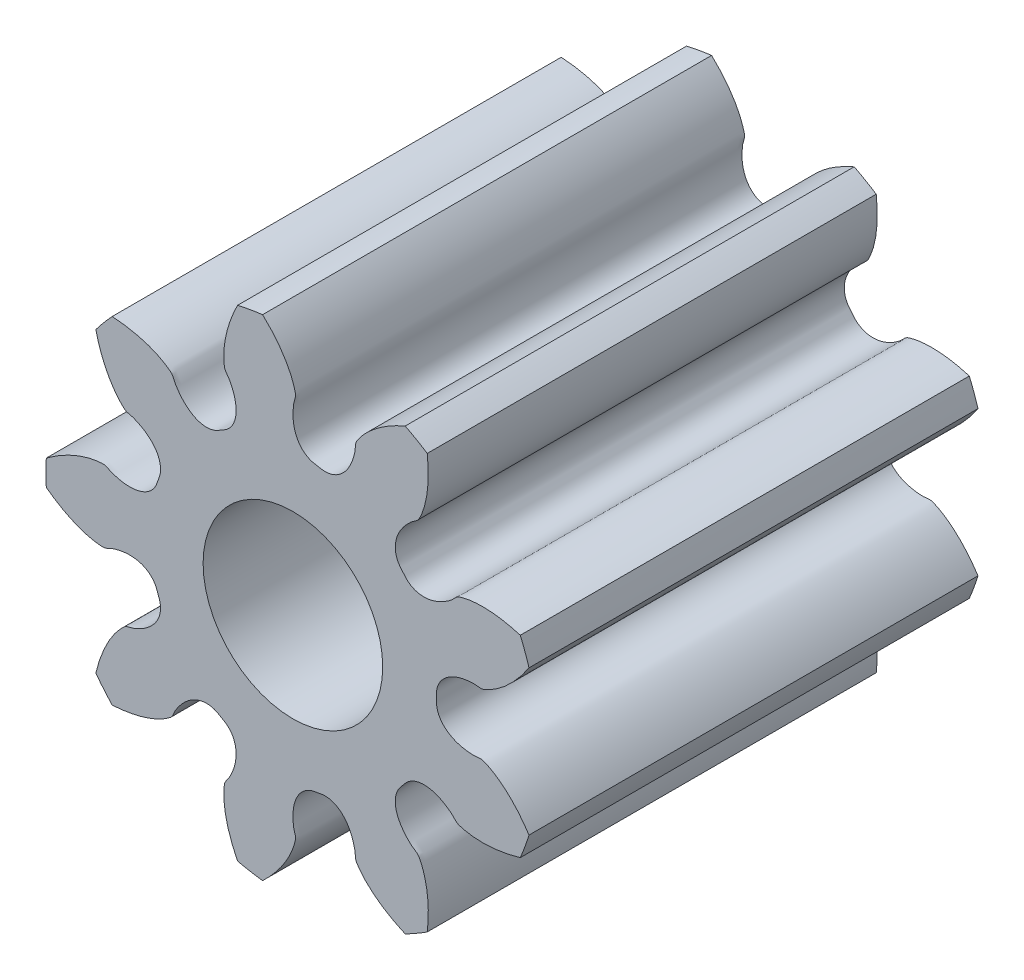
SolidWorks part; units mm, degrees
ref_plane "Front Plane" through (0, 0, 0) normal (0, 0, 1) x (1, 0, 0)
ref_plane "Top Plane" through (0, 0, 0) normal (0, 1, 0) x (1, 0, 0)
ref_plane "Right Plane" through (0, 0, 0) normal (1, 0, 0) x (0, 0, -1)
ref_axis "Axis1" through (0, 0, 55) along (0, 0, -1)
sketch "旋转草图小直齿轮" plane through (0, 0, 0) normal (1, 0, 0) x (0, 0, -1)
  line L0 (0, 0) -> (1, 0) construction
  line L1 (-2.5, 0) -> (-2.5, 2.75)
  line L2 (-2.5, 2.75) -> (2.5, 2.75)
  line L3 (2.5, 2.75) -> (2.5, 0)
  line L4 (2.5, 0) -> (-2.5, 0)
  dimension "Side1" = 2.5
  dimension "OutsideRadius" = 2.75
  dimension "Side2" = 2.5
revolve "小直齿轮" add sketch "旋转草图小直齿轮" angle 360 about L0
sketch "齿草图小直齿轮" plane through (0, 0, 0) normal (0, 0, 1) x (1, 0, 0)
  arc A0 (2.6468, 0.8337) -> (2.6468, -0.8337) centre (0, 0) cw
  spline S0 degree 3 poles (2.6468, -0.8337) (2.621, -0.7928) (2.581, -0.7345) (2.5243, -0.6624) (2.4833, -0.6146) (2.4428, -0.5713) (2.4033, -0.5325) (2.365, -0.4979) (2.3283, -0.4675) (2.2933, -0.4409) (2.2603, -0.418) (2.2297, -0.3986) (2.2015, -0.3824) (2.1761, -0.3691) (2.1467, -0.3558) (2.0963, -0.3315) (2.0402, -0.3485) (1.9927, -0.3456) (1.9689, -0.3441) (1.9455, -0.3417) (1.9227, -0.3386) (1.9004, -0.3347) (1.8787, -0.33) (1.8575, -0.3246) (1.8368, -0.3184) (1.8167, -0.3115) (1.7972, -0.3037) (1.7783, -0.2952) (1.7599, -0.2858) (1.7421, -0.2755) (1.725, -0.2644) (1.7086, -0.2523) (1.6928, -0.2392) (1.6779, -0.2251) (1.6638, -0.2099) (1.6507, -0.1936) (1.6386, -0.1762) (1.6279, -0.1576) (1.6185, -0.1379) (1.6107, -0.1172) (1.6047, -0.0956) (1.6007, -0.0732) (1.5991, -0.0533) (1.5985, -0.0288) (1.5997, 0) (1.5985, 0.0288) (1.5991, 0.0533) (1.6007, 0.0732) (1.6047, 0.0956) (1.6107, 0.1172) (1.6185, 0.1379) (1.6279, 0.1576) (1.6386, 0.1762) (1.6507, 0.1936) (1.6638, 0.2099) (1.6779, 0.2251) (1.6928, 0.2392) (1.7086, 0.2523) (1.725, 0.2644) (1.7421, 0.2755) (1.7599, 0.2858) (1.7783, 0.2952) (1.7972, 0.3037) (1.8167, 0.3115) (1.8368, 0.3184) (1.8575, 0.3246) (1.8787, 0.33) (1.9004, 0.3347) (1.9227, 0.3386) (1.9455, 0.3417) (1.9689, 0.3441) (1.9927, 0.3456) (2.0402, 0.3485) (2.0963, 0.3315) (2.1467, 0.3558) (2.1761, 0.3691) (2.2015, 0.3824) (2.2297, 0.3986) (2.2603, 0.418) (2.2933, 0.4409) (2.3283, 0.4675) (2.365, 0.4979) (2.4033, 0.5325) (2.4428, 0.5713) (2.4833, 0.6146) (2.5243, 0.6624) (2.581, 0.7345) (2.621, 0.7928) (2.6468, 0.8337) knots 0 0 0 0 0.050086 0.073153 0.094901 0.115331 0.134443 0.152236 0.168712 0.18387 0.19771 0.210231 0.221435 0.23132 0.239888 0.25501 0.287656 0.296066 0.304314 0.312407 0.320351 0.328153 0.335823 0.34337 0.350804 0.358136 0.36538 0.372549 0.379657 0.386723 0.393763 0.400797 0.407845 0.414926 0.422061 0.42927 0.436569 0.443971 0.451486 0.459115 0.466852 0.474686 0.482594 0.487541 0.5 0.512459 0.517406 0.525314 0.533148 0.540885 0.548514 0.556029 0.563431 0.57073 0.577939 0.585074 0.592155 0.599203 0.606237 0.613277 0.620343 0.627451 0.63462 0.641864 0.649196 0.65663 0.664177 0.671847 0.679649 0.687593 0.695686 0.703934 0.712344 0.74499 0.760112 0.76868 0.778565 0.789769 0.80229 0.81613 0.831288 0.847764 0.865557 0.884669 0.905099 0.926847 0.949914 1 1 1 1
extrude "齿拉伸切除小直齿轮" cut sketch "齿草图小直齿轮" against normal blind 2.5 and the other way blind 2.5
pattern_circular "齿形小直齿轮" count 9 every 40 about axis through (0, 0, 55) along (0, 0, -1) of "齿拉伸切除小直齿轮"
sketch "孔旋转草图" plane through (0, 0, 0) normal (1, 0, 0) x (0, 0, -1)
  line L0 (0, 0) -> (1, 0) construction
  line L1 (-2.5, 0) -> (2.5, 0)
  line L2 (2.5, 0) -> (2.5, 1)
  line L3 (2.5, 1) -> (-2.5, 1)
  line L4 (-2.5, 1) -> (-2.5, 0)
  dimension "BoreSide1" = 2.5
  dimension "TaperSide1" = 1
  dimension "BoreSide2" = 2.5
  dimension "TaperSide2" = 1
revolve "孔旋转切除" cut sketch "孔旋转草图" angle 360 about L0
sketch "辅助草图小直齿轮" plane through (0, 0, 0) normal (0, 0, 1) x (1, 0, 0)
  circle A0 centre (0, 0) radius 2.25 construction
  circle A1 centre (0, 0) radius 2.1143 construction
  circle A2 centre (0, 0) radius 2.2768 construction
  circle A3 centre (0, 0) radius 2.75 construction
  circle A4 centre (0, 0) radius 1.5992 construction
  dimension "PitchDiameter" = 4.5
  dimension "BaseDiameter" = 4.2286
  dimension "FormDiameter" = 4.5536
  dimension "MajorDiameter" = 5.5
  dimension "MinorDiameter" = 3.1984
